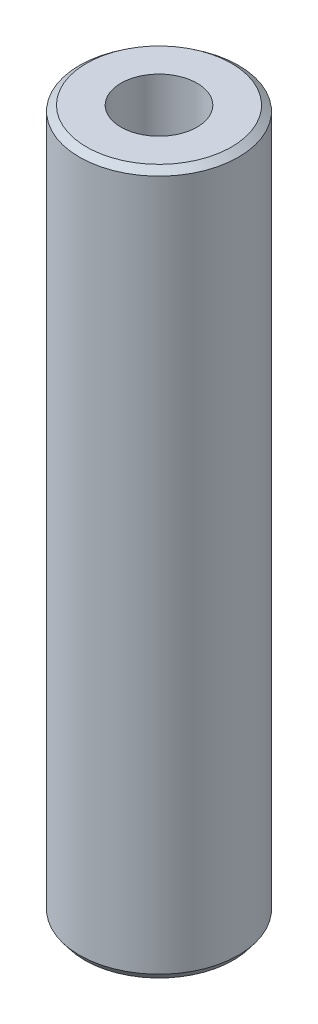
SolidWorks part; units mm, degrees
ref_plane "Front Plane" through (0, 0, 0) normal (0, 0, 1) x (1, 0, 0)
ref_plane "Top Plane" through (0, 0, 0) normal (0, 1, 0) x (1, 0, 0)
ref_plane "Right Plane" through (0, 0, 0) normal (1, 0, 0) x (0, 0, -1)
sketch "Sketch1" plane through (0, 0, 0) normal (0, 1, 0) x (1, 0, 0)
  circle A0 centre (0, 0) radius 57.5
  dimension "SHAFT_OD" = 115
extrude "Boss-Extrude1" add sketch "Sketch1" along normal blind 508.5324
sketch "Sketch2" plane through (0, 0, 0) normal (0, 1, 0) x (1, 0, 0)
  circle A0 centre (0, 0) radius 27.5376
  dimension "BORE_D" = 55.0753
extrude "Cut-Extrude1" cut sketch "Sketch2" along normal through all
chamfer "Chamfer1" distance 3.8147 angle 53.054 2 edges at (0, 508.5324, 57.5) (0, 0, 57.5) first distance on face at (0, 508.5324, 57.5) first distance on face at (0, 0, 27.5376)
